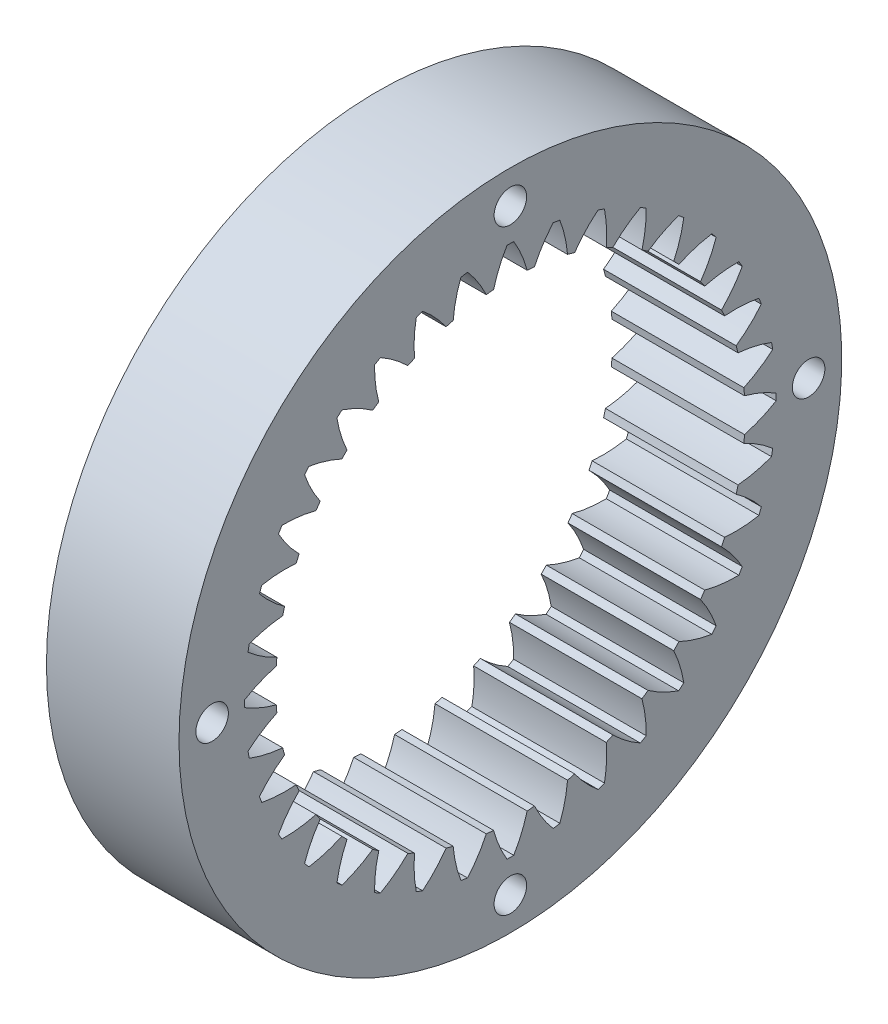
SolidWorks part; units mm, degrees
ref_plane "Plane1" through (0, 0, 0) normal (0, 0, 1) x (1, 0, 0)
ref_plane "Plane2" through (0, 0, 0) normal (0, 1, 0) x (1, 0, 0)
ref_plane "Plane3" through (0, 0, 0) normal (1, 0, 0) x (0, 0, -1)
sketch "HoldingSke" plane through (0, 0, 0) normal (0, 1, 0) x (1, 0, 0)
  line L0 (0, 0) -> (0.6472, -0.4702)
  line L1 (-15, 0) -> (100, 0) construction
  line L2 (0, 0) -> (-2.1039, 2.3779)
  line L3 (0, 0) -> (-11.863, 4.5341)
  line L4 (0, 0) -> (6.9867, 5.0761)
  line L5 (0, 0) -> (-23.7986, -8.8762)
  line L6 (0, 0) -> (-10.5278, -7.1032)
  line L7 (-2.1039, 2.3779) -> (3.3635, 27.1825)
  line L8 (-76.2, 3.6279) -> (-54.61, 3.6279)
  line L9 (-71.009, 38.7566) -> (-53.1078, 45.2721)
  line L10 (-76.2, 71.12) -> (104.1128, 71.12)
  line L11 (0, 0) -> (-12, 0)
  line L12 (-76.2, 101.6) -> (-76.155, 101.6)
  line L13 (24.9733, 27.94) -> (52.9518, 28.4284)
  line L14 (24.9733, 27.94) -> (24.9743, 27.94)
  line L15 (24.9733, 27.94) -> (100.4006, 29.5858)
  circle A0 centre (0, 0) radius 30
  circle A1 centre (0, 0) radius 12.7
  circle A2 centre (0, 0) radius 12.7
  dimension "MHD" = 25.4
  dimension "Hub_dia" = 25.4
  dimension "Diameter" = 60
  dimension "Num_teeth" = 36
  dimension "Pitch_radius" = 180.3128
  dimension "Pitch" = 0.8
  dimension "Width" = 12
  dimension "Overall_len" = 25.4
  dimension "Show_teeth" = 36
  dimension "Thickness" = 12.7
  dimension "OAL" = 25.4001
  dimension "T_dim" = 21.59
  dimension "Ap" = 20
  dimension "H" = 19.05
  dimension "Backlash" = 0.045
  dimension "Addendum_fac" = 1
  dimension "Dedendum_fac" = 1.25
  dimension "Clearance_fac" = 0.25
  dimension "Dedendum_add" = 0.001
  dimension "Module" = 1.25
sketch "BasProSke" plane through (0, 0, 0) normal (0, 1, 0) x (1, 0, 0)
  line L0 (-10, 0) -> (60, 0) construction
  line L1 (0, 21.25) -> (0, 30)
  line L2 (0, 21.25) -> (12, 21.25)
  line L3 (12, 21.25) -> (12, 30)
  line L4 (12, 30) -> (0, 30)
  dimension "Diameter" = 60
  dimension "Thickness" = 12
  dimension "Inside_diameter" = 42.5
revolve "Base-Revolve" add sketch "BasProSke" angle 360 about L0
sketch "TooCutSke" plane through (0, 0, 0) normal (1, 0, 0) x (0, 0, -1)
  line L3 (1.0939, 22.4734) -> (1.0939, 53.6633) construction
  line L4 (0, 0) -> (0, 59.563) construction
  line L5 (0, 0) -> (-5.9551, 68.0675) construction
  line L6 (-9.3468, 18.2837) -> (36.0403, 22.2546) construction
  circle A0 centre (0, 0) radius 22.5 construction
  circle A1 centre (0, 0) radius 24.0635 construction
  circle A2 centre (0, 0) radius 19.0288 construction
  circle A3 centre (0, 0) radius 21.2246 construction
  arc A4 (1.5267, 21.1696) -> (0.3061, 24.0616) centre (-9.3468, 18.2837) ccw
  arc A5 (1.5267, 21.1696) -> (-1.5267, 21.1696) centre (0, 0) ccw
  arc A6 (0.3061, 24.0616) -> (-0.3061, 24.0616) centre (0, 0) ccw
  arc A7 (-0.3061, 24.0616) -> (-1.5267, 21.1696) centre (9.3468, 18.2837) ccw
  dimension "Pitch_dia" = 45
  dimension "Base_dia" = 38.0576
  dimension "Root_dia" = 48.127
  dimension "Overcut_dia" = 42.4492
  dimension "Flank_rad" = 11.25
  dimension "Half_ang" = 5
  dimension "Half_CT" = 1.0939
extrude "ToothCut" cut sketch "TooCutSke" along normal through all
fillet "Breaks" [suppressed] radius 0.125
fillet "RootFillets" [suppressed] radius 0.3135
pattern_circular "TeethCuts" count 36 every 10 about axis through (-10, 0, 0) along (1, 0, 0) of "RootFillets", "Breaks", "ToothCut"
ref_axis "Central Axis" through (72.0684, 0, 0) along (-1, 0, 0)
sketch "Sketch1" plane through (12, 0, 0) normal (1, 0, 0) x (0, 0, -1)
  circle A0 centre (0, 27) radius 1.4732
  point P2 (0, 0)
  dimension "D1" = 2.9464
  dimension "D2" = 27
extrude "Cut-Extrude1" cut sketch "Sketch1" against normal through all
pattern_circular "CirPattern1" count 4 over 360 about axis through (72.0684, 0, 0) along (-1, 0, 0) of "Cut-Extrude1"
equation "' \"Module@HoldingSke\" = 6.35"
equation "' \"Num_teeth@HoldingSke\" = 24"
equation "' \"Ap@HoldingSke\" =  14.5"
equation "' \"Width@HoldingSke\" = 12"
equation "' \"Diameter@HoldingSke\" = 8 * 25.4"
equation "' \"Show_teeth@HoldingSke\" = 100"
equation "' \"Backlash@HoldingSke\" = 0.009 * 25.4"
equation "' \"Addendum_fac@HoldingSke\" = 1.0"
equation "' \"Dedendum_fac@HoldingSke\" = 1.25"
equation "' \"Dedendum_add@HoldingSke\" = 0.00005 * 25.4"
equation "' \"Clearance_fac@HoldingSke\" = 0.25"
equation "\"Pitch@HoldingSke\" = 1 / \"Module@HoldingSke\" "
equation "\"Overcut_dia@TooCutSke\" = (\"Num_teeth@HoldingSke\" - 2 * \"Addendum_fac@HoldingSke\") / \"Pitch@HoldingSke\" - 0.002 * 25.4"
equation "\"Pitch_dia@TooCutSke\" = \"Num_teeth@HoldingSke\" / \"Pitch@HoldingSke\""
equation "\"Base_dia@TooCutSke\" = \"Num_teeth@HoldingSke\" / \"Pitch@HoldingSke\" * cos((\"Ap@HoldingSke\"  * 3.14159265 / 180)) * 0.90"
equation "\"Root_dia@TooCutSke\" = \"Num_teeth@HoldingSke\"  / \"Pitch@HoldingSke\" + 2 *  \"Dedendum_fac@HoldingSke\"/ \"Pitch@HoldingSke\" + \"Dedendum_add@HoldingSke\" * 2"
equation "\"Half_ang@TooCutSke\" = 180 / \"Num_teeth@HoldingSke\""
equation "\"Half_CT@TooCutSke\" = \"Num_teeth@HoldingSke\" / \"Pitch@HoldingSke\" * sin((3.14159265 / 2 / \"Num_teeth@HoldingSke\")) / 2 + 10 * \"Backlash@HoldingSke\" / 4"
equation "\"Flank_rad@TooCutSke\" = \"Num_teeth@HoldingSke\" / \"Pitch@HoldingSke\" / 4"
equation "\"Radius@RootFillets\"= \"Clearance_fac@HoldingSke\" / \"Pitch@HoldingSke\" + \"Dedendum_add@HoldingSke\""
equation "\"Break_rad@Breaks\" = 0.02 / \"Pitch@HoldingSke\" * 5"
equation "\"Num_teeth@TeethCuts\" = int( \"Show_teeth@HoldingSke\" ) + 1"
equation "\"Num_teeth@TeethCuts\" = ((sgn( \"Num_teeth@TeethCuts\" - \"Num_teeth@HoldingSke\" )-1)*( \"Num_teeth@TeethCuts\" - \"Num_teeth@HoldingSke\" ))/-2+ \"Num_teeth@HoldingSke\""
equation "\"Num_teeth@TeethCuts\" = ((sgn( \"Num_teeth@TeethCuts\" - 2.0)+1)*( \"Num_teeth@TeethCuts\" - 2.0))/2 +2.0"
equation "\"Angle@TeethCuts\" = 360.0 / \"Num_teeth@HoldingSke\""
equation "\"Diameter@BasProSke\" = \"Num_teeth@HoldingSke\"  / \"Pitch@HoldingSke\" + 2 *  \"Dedendum_fac@HoldingSke\"/ \"Pitch@HoldingSke\" + \"Dedendum_add@HoldingSke\" * 2 + 0.002 * 25.4"
equation "\"Diameter@BasProSke\" = ((sgn( \"Diameter@BasProSke\"  - \"Diameter@HoldingSke\" )+1)*( \"Diameter@BasProSke\"  - \"Diameter@HoldingSke\" ))/2 + \"Diameter@HoldingSke\""
equation "\"Inside_diameter@BasProSke\" =  (\"Num_teeth@HoldingSke\" - 2 * \"Addendum_fac@HoldingSke\") / \"Pitch@HoldingSke\" "
equation "\"Thickness@BasProSke\"  = \"Width@HoldingSke\""
